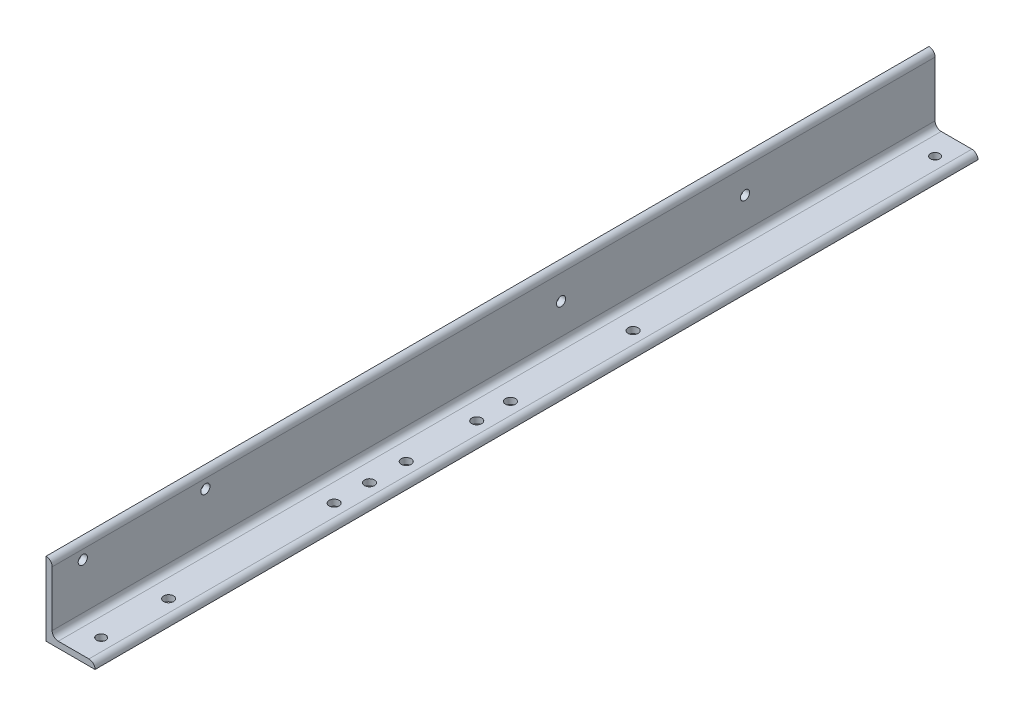
SolidWorks part; units mm, degrees
ref_plane "Front Plane" through (0, 0, 0) normal (0, 0, 1) x (1, 0, 0)
ref_plane "Top Plane" through (0, 0, 0) normal (0, 1, 0) x (1, 0, 0)
ref_plane "Right Plane" through (0, 0, 0) normal (1, 0, 0) x (0, 0, -1)
sketch "Sketch1" plane through (0, 0, 0) normal (0, 0, 1) x (1, 0, 0)
  line L0 (0, 0) -> (0, 152.4)
  line L1 (0, 152.4) -> (0.0051, 152.4)
  line L2 (12.7, 139.7051) -> (12.7, 25.4)
  line L3 (25.4, 12.7) -> (88.9051, 12.7)
  line L4 (101.6, 0.0051) -> (101.6, 0)
  line L5 (101.6, 0) -> (0, 0)
  arc A0 (101.6, 0.0051) -> (88.9051, 12.7) centre (88.9051, 0.0051) ccw
  arc A1 (0.0051, 152.4) -> (12.7, 139.7051) centre (0.0051, 139.7051) cw
  arc A2 (25.4, 12.7) -> (12.7, 25.4) centre (25.4, 25.4) cw
  circle A3 centre (0, 0) radius 12.7 construction
  dimension "D2" = 0.0051
  dimension "Radius_1" = 12.7
  dimension "Radius_2" = 12.7
  dimension "D1" = 12.7
  dimension "V_leg" = 152.4
  dimension "H_leg" = 101.6
  dimension "Thickness" = 12.7
  dimension "Flat_wid" = 0.0051
extrude "Boss-Extrude1" add sketch "Sketch1" along normal mid plane 1828.8
sketch "Sketch3" plane through (0, 12.7, 0) normal (0, 1, 0) x (1, 0, 0)
  line L0 (63.5, -964.9914) -> (63.5, 988.9202) construction
  line L1 (101.6, -914.4) -> (101.6, 914.4) construction
  line L2 (88.9051, -914.4) -> (25.4, -914.4) construction
  line L3 (88.9051, 914.4) -> (25.4, 914.4) construction
  circle A0 centre (63.5, -863.6) radius 9.525
  circle A1 centre (63.5, 863.6) radius 9.525
  circle A2 centre (63.5, -723.9) radius 10.3187
  circle A3 centre (63.5, -381) radius 10.3188
  circle A4 centre (63.5, -15.875) radius 10.3187
  circle A5 centre (63.5, -231.775) radius 10.3187
  circle A6 centre (63.5, 238.125) radius 10.3187
  circle A7 centre (63.5, -307.975) radius 10.3188
  circle A8 centre (63.5, -85.725) radius 10.3188
  dimension "D3" = 50.8
  dimension "D4" = 190.5
  dimension "D5" = 342.9
  dimension "D8" = 254
  dimension "D9" = 20.6375
  dimension "D10" = 222.25
  dimension "D11" = 606.425
  dimension "D7" = 76.2
  dimension "D1" = 38.1
  dimension "D2" = 50.8
  dimension "D6" = 69.85
extrude "Cut-Extrude2" cut sketch "Sketch3" against normal up to next
sketch "Sketch4" plane through (12.7, 0, 0) normal (1, 0, 0) x (0, 0, -1)
  line L0 (-914.4, 152.4) -> (914.4, 152.4) construction
  line L1 (-914.4, 25.4) -> (-914.4, 139.7051) construction
  line L2 (914.4, 25.4) -> (914.4, 139.7051) construction
  circle A0 centre (-850.9, 120.65) radius 9.525
  circle A1 centre (-596.9, 120.65) radius 9.525
  circle A2 centre (139.7, 88.9) radius 9.525
  circle A3 centre (520.7, 88.9) radius 9.525
  dimension "D1" = 31.75
  dimension "D4" = 254
  dimension "D2" = 31.75
  dimension "D3" = 63.5
  dimension "D5" = 63.5
  dimension "D6" = 774.7
  dimension "D7" = 63.5
  dimension "D8" = 393.7
  dimension "3/4\" Clearance Hole" = 19.05
extrude "Cut-Extrude3" cut sketch "Sketch4" against normal up to next
equation "\"D3@Sketch3\" = \"D2@Sketch3\""
